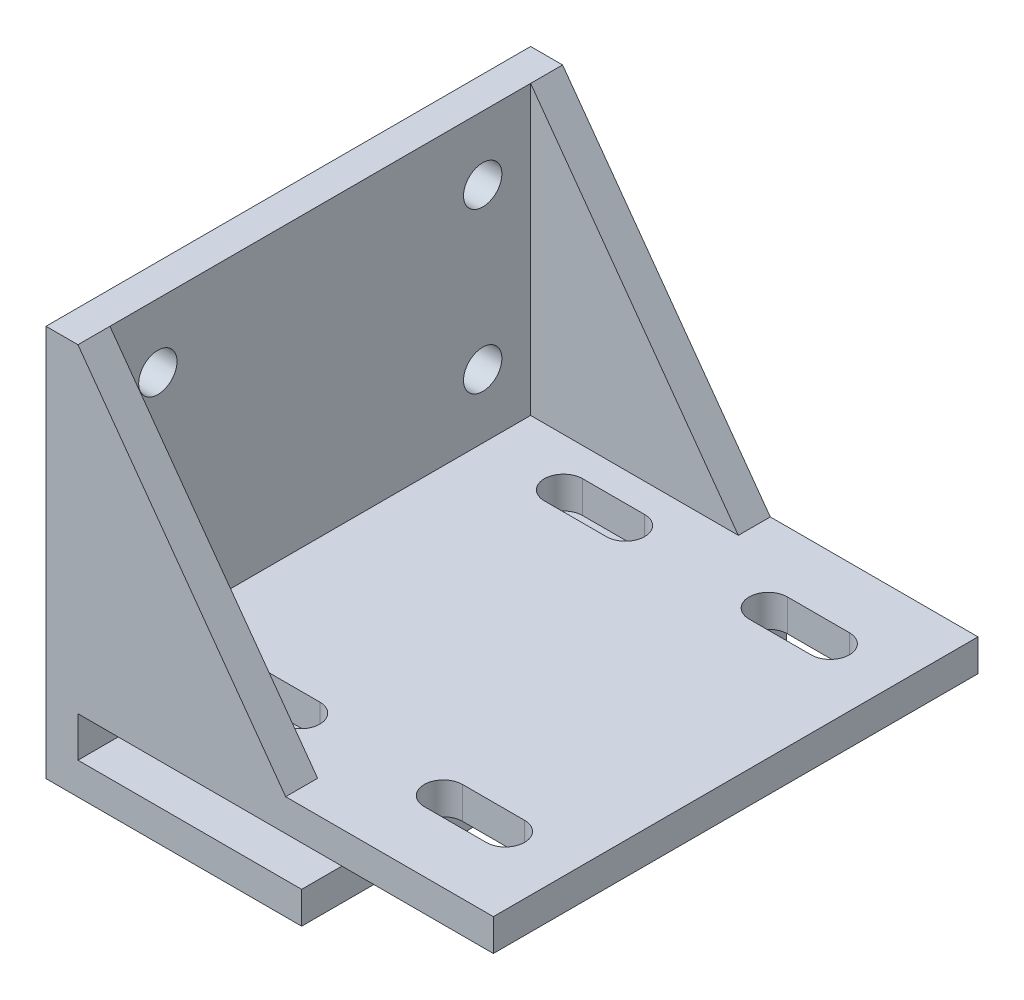
SolidWorks part; units mm, degrees
ref_plane "Front Plane" through (0, 0, 0) normal (0, 0, 1) x (1, 0, 0)
ref_plane "Top Plane" through (0, 0, 0) normal (0, 1, 0) x (1, 0, 0)
ref_plane "Right Plane" through (0, 0, 0) normal (1, 0, 0) x (0, 0, -1)
sketch "Sketch1" plane through (0, 0, 0) normal (0, 1, 0) x (1, 0, 0)
  line L1 (-30.1722, 4.0464) -> (39.8278, 4.0464)
  line L2 (-30.1722, 4.0464) -> (-30.1722, -10.9536)
  line L3 (-30.1722, -10.9536) -> (39.8278, -10.9536)
  line L4 (39.8278, 4.0464) -> (39.8278, -10.9536)
  dimension "D1" = 15
  dimension "D2" = 70
extrude "Boss-Extrude1" add sketch "Sketch1" along normal blind 5
sketch "Sketch3" plane through (0, 5, 0) normal (0, 1, 0) x (1, 0, 0)
  line L0 (-30.1722, 4.0464) -> (-25.1722, 4.0464)
  line L1 (39.8278, 4.0464) -> (-30.1722, 4.0464) construction
  line L2 (-30.1722, -10.9536) -> (-25.1722, -10.9536)
  line L3 (-30.1722, -10.9536) -> (39.8278, -10.9536) construction
  line L4 (-25.1722, 4.0464) -> (-25.1722, -10.9536)
  line L5 (-30.1722, 4.0464) -> (-30.1722, -10.9536)
extrude "Boss-Extrude2" add sketch "Sketch3" along normal blind 45
sketch "Sketch4" plane through (-30.1722, 0, 0) normal (-1, 0, 0) x (0, 0, 1)
  line L0 (3.4536, 0) -> (3.4536, 50)
  line L2 (-4.0464, 0) -> (10.9536, 0) construction
  line L3 (3.4536, 0) -> (3.4536, 15)
  line L4 (3.4536, 50) -> (3.4536, 40)
hole_wizard "Ø6.0mm Dowel Hole1" positions "Sketch5" profile "Sketch6" hole size "Ø6.0" standard "ANSI Metric" end condition up to next
sketch "Sketch5" plane through (-30.1722, 0, 0) normal (-1, 0, 0) x (0, 0, 1)
  point P3 (3.4536, 15)
  point P7 (3.4536, 40)
sketch "Sketch6" plane through (-30.1722, 15, 3.4536) normal (0, 1, 0) x (0, 0, 1)
  line L0 (0, 0) -> (0, 5)
  line L1 (0, 5) -> (3, 5)
  line L2 (3, 5) -> (3, 0)
  line L5 (3, 0) -> (0, 0)
  line L11 (0, -6.35) -> (0, 107.95) construction
  dimension "Thru Hole Dia." = 6
  dimension "Thru Hole Depth" = 5
sketch "Sketch7" plane through (0, 0, 0) normal (0, -1, 0) x (1, 0, 0)
  line L0 (-30.1722, 3.4536) -> (39.8278, 3.4536)
  line L1 (-30.1722, -4.0464) -> (-30.1722, 10.9536) construction
  line L2 (39.8278, 10.9536) -> (39.8278, -4.0464) construction
hole_wizard "Ø6.0mm Dowel Slot1" positions "Sketch8" profile "Sketch9" size "Ø6.0" standard "ANSI Metric" slot yes end condition up to next
sketch "Sketch8" plane through (0, 5, 0) normal (0, 1, 0) x (1, 0, 0)
  line L0 (-15.5307, -3.4536) -> (0.1693, -3.4536) construction
  point P0 (-7.6807, -3.4536)
  point P5 (24.3593, -3.4534)
  dimension "D1" = 15.7
sketch "Sketch9" plane through (-7.6807, 5, 3.4536) normal (1, 0, 0) x (0, 0, 1)
  line L0 (0, 0) -> (0, 5)
  line L1 (0, 5) -> (3, 5)
  line L2 (3, 5) -> (3, 0)
  line L5 (3, 0) -> (0, 0)
  line L11 (0, -6.35) -> (0, 107.95) construction
  dimension "Thru Hole Dia." = 6
  dimension "Thru Hole Depth" = 5
sketch "Sketch10" plane through (0, 0, -4.0464) normal (0, 0, -1) x (-1, 0, 0)
  line L0 (-39.8278, 5) -> (-39.8278, 0)
  line L1 (-39.8278, 0) -> (30.1722, 0)
  line L2 (30.1722, 0) -> (30.1722, 50)
  line L3 (30.1722, 50) -> (25.1722, 50)
  line L4 (25.1722, 50) -> (25.1722, 5)
  line L5 (25.1722, 5) -> (-39.8278, 5)
extrude "Boss-Extrude3" add sketch "Sketch10" along normal blind 50.83
hole_wizard "Ø6.0mm Dowel Slot2" positions "Sketch11" profile "Sketch12" size "Ø6.0" standard "ANSI Metric" slot yes end condition up to next
sketch "Sketch11" plane through (0, 5, 0) normal (0, 1, 0) x (1, 0, 0)
  line L0 (-15.5307, 47.3764) -> (0.1693, 47.3764) construction
  point P0 (-7.6807, 47.3764)
  point P5 (24.3593, 47.3766)
  dimension "D1" = 15.7
sketch "Sketch12" plane through (-7.6807, 5, -47.3764) normal (1, 0, 0) x (0, 0, 1)
  line L0 (0, 0) -> (0, 5)
  line L1 (0, 5) -> (3, 5)
  line L2 (3, 5) -> (3, 0)
  line L5 (3, 0) -> (0, 0)
  line L11 (0, -6.35) -> (0, 107.95) construction
  dimension "Thru Hole Dia." = 6
  dimension "Thru Hole Depth" = 5
sketch "Sketch13" plane through (0, 5, 0) normal (0, 1, 0) x (1, 0, 0)
  line L0 (-15.5307, 47.3764) -> (-25.1722, 47.3764)
  line L1 (-25.1722, -10.9536) -> (-25.1722, 54.8764) construction
  arc A0 (-12.5307, 50.3764) -> (-12.5307, 44.3764) centre (-12.5307, 47.3764) ccw construction
sketch "Sketch14" plane through (-25.1722, 0, 0) normal (1, 0, 0) x (0, 0, -1)
  line L0 (47.3764, 5) -> (47.3764, 50)
  line L1 (-10.9536, 50) -> (54.8764, 50) construction
  line L2 (47.3764, 50) -> (47.3764, 40)
  line L3 (47.3764, 5) -> (47.3764, 15)
hole_wizard "Ø6.0mm Dowel Hole2" positions "Sketch15" profile "Sketch16" hole size "Ø6.0" standard "ANSI Metric"
sketch "Sketch15" plane through (-25.1722, 0, 0) normal (1, 0, 0) x (0, 0, -1)
  point P0 (47.3764, 40)
  point P3 (47.3764, 15)
sketch "Sketch16" plane through (-25.1722, 40, -47.3764) normal (0, 1, 0) x (0, 0, -1)
  line L0 (0, 0) -> (0, 9.8016)
  line L1 (0, 9.8016) -> (3, 7.999)
  line L2 (3, 7.999) -> (3, 0)
  line L5 (3, 0) -> (0, 0)
  line L10 (0, 9.8016) -> (-3, 7.999) construction
  line L11 (0, -6.35) -> (0, 107.95) construction
  dimension "Hole Dia." = 6
  dimension "Hole Depth" = 7.999
  dimension "Drill Angle" = 118
sketch "Sketch17" plane through (0, 0, 10.9536) normal (0, 0, 1) x (1, 0, 0)
  line L0 (-25.1722, 50) -> (7.3278, 5)
  line L1 (-25.1722, 5) -> (39.8278, 5) construction
  line L3 (-30.1722, 0) -> (39.8278, 0) construction
  line L4 (7.3278, 0) -> (-30.1722, 0)
  line L5 (-30.1722, 50) -> (-30.1722, 0) construction
  line L6 (-30.1722, 0) -> (-30.1722, 50)
  line L7 (-30.1722, 50) -> (-25.1722, 50)
  line L8 (7.3278, 5) -> (39.8278, 5)
  line L9 (39.8278, 5) -> (39.8278, 0)
  line L17 (-30.1722, 0) -> (39.8278, 0)
  line L18 (39.8278, 0) -> (39.8278, 5)
  line L19 (39.8278, 5) -> (-25.1722, 5)
  line L20 (-25.1722, 5) -> (-25.1722, 50)
  line L21 (-25.1722, 50) -> (-30.1722, 50)
  line L22 (-30.1722, 50) -> (-30.1722, 0)
  line L23 (7.3278, 0) -> (39.8278, 0)
  dimension "D1" = 0
extrude "Boss-Extrude4" add sketch "Sketch17" along normal blind 5
sketch "Sketch18" plane through (0, 0, -54.8764) normal (0, 0, -1) x (-1, 0, 0)
  line L0 (25.1722, 50) -> (-7.3278, 5)
  line L1 (25.1722, 5) -> (-39.8278, 5) construction
  line L2 (-7.3278, 5) -> (-39.8278, 5)
  line L3 (-39.8278, 5) -> (-39.8278, 0)
  line L4 (-39.8278, 0) -> (30.1722, 0)
  line L5 (30.1722, 0) -> (30.1722, 50)
  line L6 (30.1722, 50) -> (25.1722, 50)
extrude "Boss-Extrude5" add sketch "Sketch18" along normal blind 5
sketch "Sketch19" plane through (0, 0, 0) normal (0, -1, 0) x (1, 0, 0)
  line L0 (-30.1722, -59.8764) -> (-30.1722, 15.9536)
  line L1 (-30.1722, -59.8764) -> (-25.1722, -59.8764)
  line L2 (39.8278, -59.8764) -> (-30.1722, -59.8764) construction
  line L3 (-30.1722, 15.9536) -> (-25.1722, 15.9536)
  line L4 (-30.1722, 15.9536) -> (39.8278, 15.9536) construction
  line L5 (-25.1722, -59.8764) -> (-25.1722, 15.9536)
extrude "Boss-Extrude6" add sketch "Sketch19" along normal blind 11.3
sketch "Sketch20" plane through (-25.1722, 0, 0) normal (1, 0, 0) x (0, 0, -1)
  line L0 (-15.9536, -11.3) -> (-15.9536, -6.3)
  line L1 (-15.9536, -11.3) -> (-15.9536, 0) construction
  line L2 (-15.9536, -6.3) -> (59.8764, -6.3)
  line L3 (59.8764, -11.3) -> (59.8764, 0) construction
  line L4 (59.8764, -6.3) -> (59.8764, -11.3)
  line L5 (59.8764, -11.3) -> (-15.9536, -11.3)
extrude "Boss-Extrude7" add sketch "Sketch20" along normal blind 35
sketch "Sketch25" plane through (0, 5, 0) normal (0, 1, 0) x (1, 0, 0)
  line L0 (-7.6807, 50.3764) -> (-7.6807, 44.3764)
  line L1 (-12.5307, 50.3764) -> (-2.8307, 50.3764) construction
  line L2 (-12.5307, 44.3764) -> (-2.8307, 44.3764) construction
  line L3 (-7.6807, 44.3764) -> (-7.6807, 47.3764)
  line L4 (-7.6807, 47.3764) -> (0.1693, 47.3764)
  line L5 (-7.6807, -0.4536) -> (-7.6807, -6.4536)
  line L6 (-12.5307, -0.4536) -> (-2.8307, -0.4536) construction
  line L7 (-12.5307, -6.4536) -> (-2.8307, -6.4536) construction
  line L8 (-7.6807, -6.4536) -> (-7.6807, -3.4536)
  line L9 (-7.6807, -3.4536) -> (0.1693, -3.4536)
  arc A0 (-2.8307, 44.3764) -> (-2.8307, 50.3764) centre (-2.8307, 47.3764) ccw construction
  arc A1 (-2.8307, -6.4536) -> (-2.8307, -0.4536) centre (-2.8307, -3.4536) ccw construction
hole_wizard "Ø6.0mm Dowel Slot3" positions "Sketch26" profile "Sketch27" size "Ø6.0" standard "ANSI Metric" slot yes end condition through all
sketch "Sketch26" plane through (0, 5, 0) normal (0, 1, 0) x (1, 0, 0)
  line L0 (-15.5307, 47.3764) -> (0.1693, 47.3764) construction
  point P0 (-7.6807, 47.3764)
  point P5 (-7.6807, -3.4536)
  dimension "D1" = 15.7
sketch "Sketch27" plane through (-7.6807, 5, -47.3764) normal (1, 0, 0) x (0, 0, 1)
  line L0 (0, 0) -> (0, 16.3)
  line L1 (0, 16.3) -> (3, 16.3)
  line L2 (3, 16.3) -> (3, 0)
  line L5 (3, 0) -> (0, 0)
  line L11 (0, -6.35) -> (0, 107.95) construction
  dimension "Thru Hole Dia." = 6
  dimension "Thru Hole Depth" = 16.3
sketch "Sketch28" plane through (-25.1722, 0, 0) normal (1, 0, 0) x (0, 0, -1)
  line L0 (-15.9536, 0) -> (21.9614, 0)
  line L1 (59.8764, 0) -> (-15.9536, 0) construction
sketch "Sketch29" plane through (0, 0, 0) normal (0, -1, 0) x (1, 0, 0)
  line L0 (39.8278, -21.9614) -> (-25.1722, -21.9614)
  line L1 (39.8278, 15.9536) -> (39.8278, -59.8764) construction
